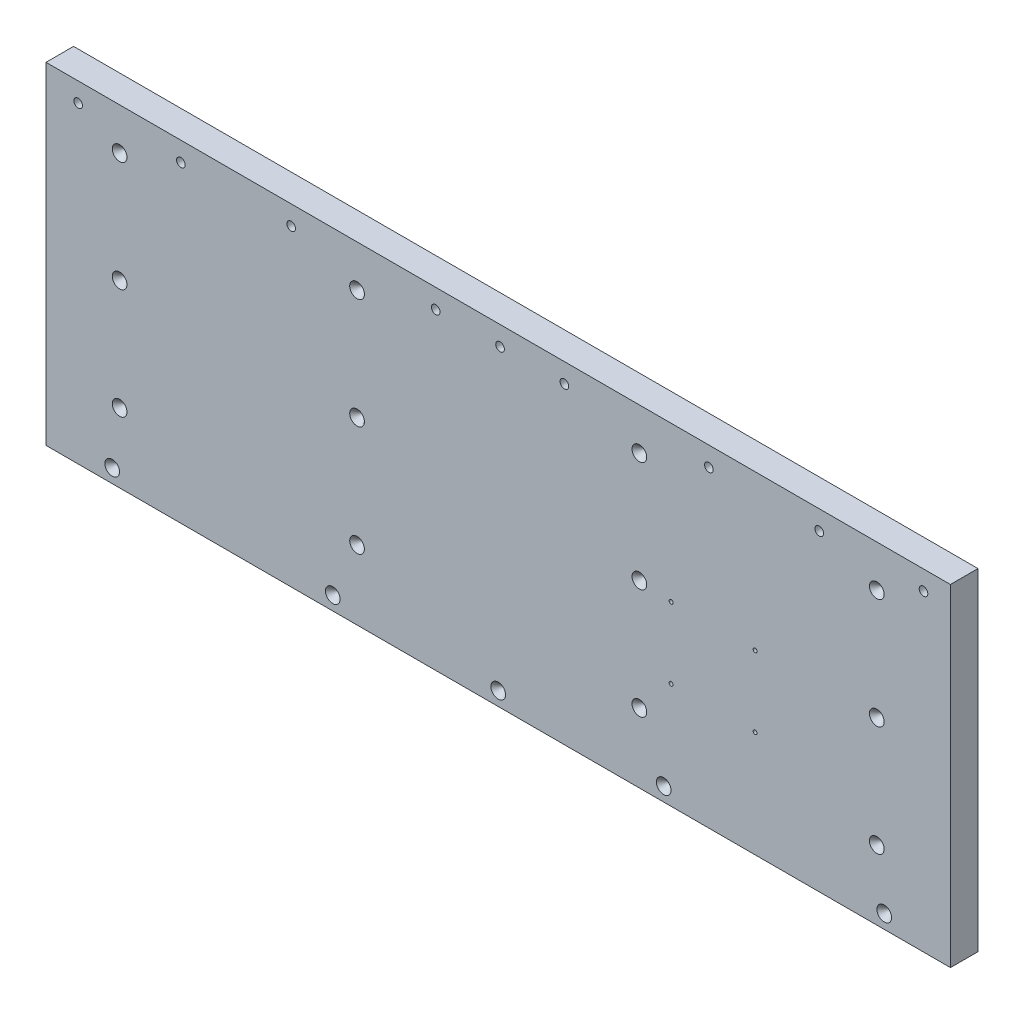
SolidWorks part; units mm, degrees
material "MDF"
ref_plane "Front Plane" through (0, 0, 0) normal (0, 0, 1) x (1, 0, 0)
ref_plane "Top Plane" through (0, 0, 0) normal (0, 1, 0) x (1, 0, 0)
ref_plane "Right Plane" through (0, 0, 0) normal (1, 0, 0) x (0, 0, -1)
sketch "Sketch1" plane through (0, 0, 0) normal (0, 0, 1) x (1, 0, 0)
  line L0 (128.7463, -697.8385) -> (128.7463, -132.715) construction
  line L1 (-496.0937, -132.715) -> (128.7463, -132.715)
  line L2 (-496.0937, -132.715) -> (-496.0937, -361.95)
  line L3 (-496.0937, -361.95) -> (128.7463, -361.95)
  line L4 (128.7463, -132.715) -> (128.7463, -361.95)
  line L5 (-496.0937, -132.715) -> (-496.0937, -697.8385) construction
  line L12 (128.7463, -132.715) -> (-84.6137, -132.715) construction
  line L13 (-290.722, -342.9) -> (-271.672, -342.9) construction
  dimension "D1" = 19.05
extrude "Boss-Extrude1" add sketch "Sketch1" along normal blind 19.05
hole_wizard "5/64 (0.07813) Diameter Hole1" positions "Sketch5" profile "Sketch6" hole size "5/64" standard "ANSI Inch"
sketch "Sketch5" plane through (-182.4037, -6471.4599, 19.05) normal (0, 0, 1) x (1, 0, 0)
  line L1 (-1.27, 6109.5099) -> (-1.27, 6338.7449) construction
  point P0 (-262.8265, 6157.4524)
  point P6 (-98.7933, 6157.4524)
  point P18 (-262.8265, 6233.6524)
  point P19 (-98.7933, 6233.6524)
  point P22 (-262.8265, 6309.8524)
  point P23 (-98.7933, 6309.8524)
  point P24 (-267.97, 6119.0349)
  point P34 (-115.57, 6119.0349)
  point P37 (-1.27, 6119.0349)
  point P40 (113.03, 6119.0349)
  point P44 (265.43, 6119.0349)
  point P55 (96.2533, 6309.8524)
  point P56 (260.2865, 6309.8524)
  point P59 (96.2533, 6233.6524)
  point P60 (260.2865, 6233.6524)
  point P63 (96.2533, 6157.4524)
  point P64 (260.2865, 6157.4524)
sketch "Sketch6" plane through (-445.2302, -314.0075, 19.05) normal (1, 0, 0) x (0, -1, 0)
  line L0 (0, 0) -> (0, 38.6962)
  line L1 (0, 38.6962) -> (0.9923, 38.1)
  line L2 (0.9923, 38.1) -> (0.9923, 4.7024)
  line L3 (0.9923, 4.7024) -> (5.08, 0)
  line L4 (5.08, 0) -> (0, 0)
  line L5 (-0.9923, 4.7024) -> (-5.08, 0) construction
  line L6 (0, 38.6962) -> (-0.9923, 38.1) construction
  line L7 (0, -6.35) -> (0, 107.95) construction
  dimension "Hole Dia." = 1.9845
  dimension "Hole Depth" = 38.1
  dimension "Near C'Sink Dia." = 10.16
  dimension "Near C'Sink Angle" = 82
  dimension "Drill Angle" = 118
hole_wizard "15/64 (0.23438) Diameter Hole1" positions "Sketch7" profile "Sketch8" hole size "15/64" standard "ANSI Inch" end condition up to next
sketch "Sketch7" plane through (0, 0, 0) normal (0, 0, -1) x (-1, 0, 0)
  point P0 (402.9075, -146.05)
  point P2 (326.7075, -146.05)
  point P4 (226.8537, -146.05)
  point P6 (182.4037, -146.05)
  point P8 (137.9537, -146.05)
  point P10 (38.1, -146.05)
  point P12 (-38.1, -146.05)
  point P13 (473.8687, -146.05)
  point P17 (-110.1471, -146.05)
sketch "Sketch8" plane through (-402.9075, -146.05, 0) normal (1, 0, 0) x (0, 1, 0)
  line L0 (0, 0) -> (0, 19.05)
  line L1 (0, 19.05) -> (2.9766, 19.05)
  line L2 (2.9766, 19.05) -> (2.9766, 0)
  line L5 (2.9766, 0) -> (0, 0)
  line L11 (0, -6.35) -> (0, 107.95) construction
  dimension "Thru Hole Dia." = 5.9533
  dimension "Thru Hole Depth" = 19.05
sketch "Sketch9" plane through (0, 0, 0) normal (0, 0, -1) x (-1, 0, 0)
  line L0 (0, -157.1498) -> (0, -342.9) construction
  line L1 (0, -250.0249) -> (93.1355, -250.0249) construction
  line L2 (61.3728, -330.2) -> (-61.3728, -330.2)
  line L3 (61.3728, -330.2) -> (61.3728, -169.8498)
  line L4 (61.3728, -169.8498) -> (-61.3728, -169.8498)
  line L5 (-61.3728, -330.2) -> (-61.3728, -169.8498)
  line L6 (61.3728, -330.2) -> (-61.3728, -169.8498) construction
  line L7 (61.3728, -169.8498) -> (-61.3728, -330.2) construction
  line L8 (93.1355, -250.0249) -> (271.672, -250.0249) construction
  line L9 (364.8075, -157.1625) -> (364.8075, -342.9) construction
  line L10 (258.972, -330.2) -> (105.8355, -330.2)
  line L11 (258.972, -330.2) -> (258.972, -169.8498)
  line L12 (258.972, -169.8498) -> (105.8355, -169.8498)
  line L13 (105.8355, -330.2) -> (105.8355, -169.8498)
  line L14 (258.972, -330.2) -> (105.8355, -169.8498) construction
  line L15 (258.972, -169.8498) -> (105.8355, -330.2) construction
  line L17 (426.1802, -330.2127) -> (303.4347, -330.2127)
  line L18 (426.1802, -330.2127) -> (426.1802, -169.8498)
  line L19 (426.1802, -169.8498) -> (303.4347, -169.8498)
  line L20 (303.4347, -330.2127) -> (303.4347, -169.8498)
  line L21 (426.1802, -330.2127) -> (303.4347, -169.8498) construction
  line L22 (426.1802, -169.8498) -> (303.4347, -330.2127) construction
  point P3 (0, -250.0249)
  point P8 (-74.0728, -342.9)
  point P13 (182.4037, -250.0249)
  point P20 (364.8075, -250.0313)
  dimension "D1" = 12.7
  dimension "D2" = 12.7
  dimension "D3" = 12.7
extrude "Cut-Extrude1" [suppressed] cut sketch "Sketch9" against normal up to next
fillet "Fillet1" [suppressed] radius 12.7
hole_wizard "#2 Clearance Hole1" positions "Sketch10" profile "Sketch11" hole size "#2" standard "ANSI Inch" end condition up to next
sketch "Sketch10" plane through (0, 0, 19.05) normal (0, 0, 1) x (1, 0, 0)
  point P2 (-6.2354, -239.6)
  point P4 (-64.2354, -239.6)
  point P6 (-64.2354, -288.6)
  point P8 (-6.2354, -288.6)
sketch "Sketch11" plane through (-6.2354, -239.6, 19.05) normal (1, 0, 0) x (0, -1, 0)
  line L0 (0, 0) -> (0, 19.05)
  line L1 (0, 19.05) -> (1.3525, 19.05)
  line L2 (1.3525, 19.05) -> (1.3525, 0)
  line L5 (1.3525, 0) -> (0, 0)
  line L11 (0, -6.35) -> (0, 107.95) construction
  dimension "Thru Hole Dia." = 2.7051
  dimension "Thru Hole Depth" = 19.05
